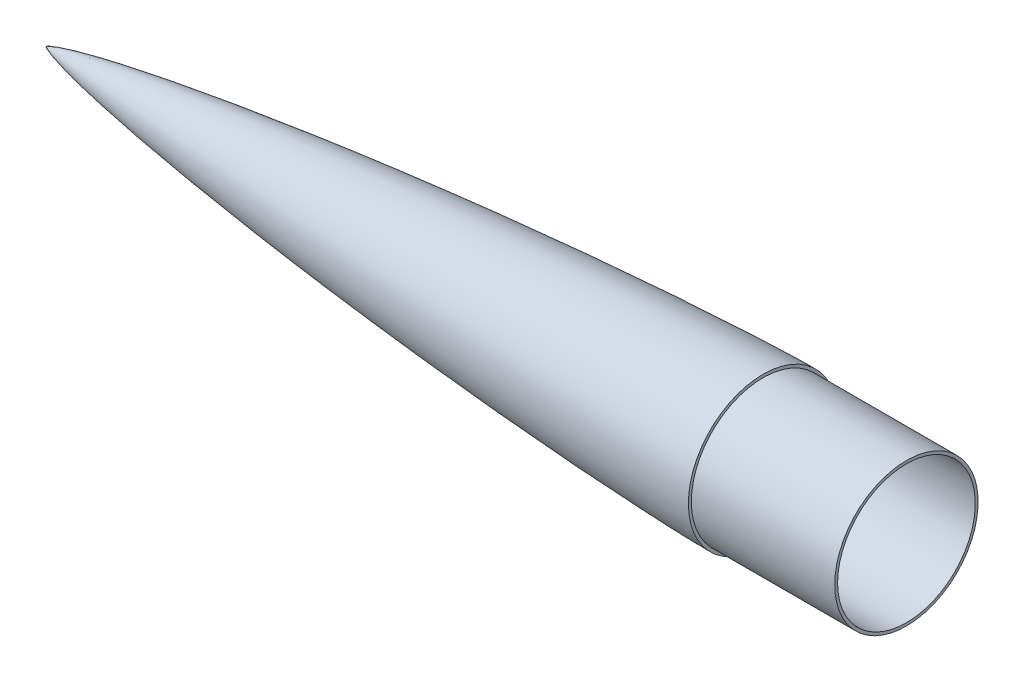
SolidWorks part; units mm, degrees
ref_plane "Front Plane" through (0, 0, 0) normal (0, 0, 1) x (1, 0, 0)
ref_plane "Top Plane" through (0, 0, 0) normal (0, 1, 0) x (1, 0, 0)
ref_plane "Right Plane" through (0, 0, 0) normal (1, 0, 0) x (0, 0, -1)
ref_axis "Axis1" through (-22.86, 0, 0) along (1, 0, 0)
sketch "Sketch1" plane through (0, 0, 0) normal (0, 0, 1) x (1, 0, 0)
  line L0 (381, 0) -> (0, 0)
  line L1 (251.46, 0) -> (-251.46, 0) construction
  line L2 (381, 0) -> (381, 36.576)
  line L4 (381, 38.1) -> (457.2, 38.1)
  line L5 (457.2, 38.1) -> (457.2, 36.576)
  line L6 (457.2, 36.576) -> (381, 36.576)
  line L7 (381, 38.1) -> (381, 39.6748)
  spline S0 degree 4 poles (0, 0) (0.003, 0.0074) (0.0105, 0.0213) (0.0311, 0.0458) (0.0656, 0.0788) (0.1085, 0.1142) (0.1696, 0.1593) (0.2429, 0.2084) (0.3536, 0.2764) (0.5216, 0.37) (0.7712, 0.4962) (1.1804, 0.6832) (1.8685, 0.9654) (3.0994, 1.4129) (5.367, 2.1346) (9.5884, 3.2967) (16.8729, 5.0187) (29.3641, 7.5637) (46.5722, 10.5749) (67.5031, 13.8025) (90.9083, 17.0332) (114.35, 19.9843) (137.8197, 22.7032) (161.3118, 25.2203) (184.8229, 27.5534) (208.3505, 29.7136) (231.8929, 31.7062) (255.4488, 33.5316) (279.0174, 35.1854) (302.5981, 36.6571) (323.2415, 37.7687) (340.9432, 38.5739) (355.1716, 39.1048) (364.7115, 39.3936) (372.5129, 39.5736) (377.3625, 39.648) (379.7875, 39.6717) (381, 39.6748) knots 0 0 0 0 0 0.000083 0.000166 0.000331 0.000497 0.000662 0.000957 0.001251 0.00185 0.002667 0.00387 0.005939 0.009599 0.016314 0.028666 0.051563 0.087599 0.14916 0.21072 0.272281 0.333842 0.395403 0.456964 0.518524 0.580085 0.641646 0.703207 0.764768 0.826328 0.887889 0.91867 0.94945 0.974725 0.987363 1 1 1 1 1 construction
  spline S1 degree 4 poles (0, 0) (0.003, 0.0074) (0.0105, 0.0213) (0.0311, 0.0458) (0.0656, 0.0788) (0.1085, 0.1142) (0.1696, 0.1593) (0.2429, 0.2084) (0.3536, 0.2764) (0.5216, 0.37) (0.7712, 0.4962) (1.1804, 0.6832) (1.8685, 0.9654) (3.0994, 1.4129) (5.367, 2.1346) (9.5884, 3.2967) (16.8729, 5.0187) (29.3641, 7.5637) (46.5722, 10.5749) (67.5031, 13.8025) (90.9083, 17.0332) (114.35, 19.9843) (137.8197, 22.7032) (161.3118, 25.2203) (184.8229, 27.5534) (208.3505, 29.7136) (231.8929, 31.7062) (255.4488, 33.5316) (279.0174, 35.1854) (302.5981, 36.6571) (323.2415, 37.7687) (340.9432, 38.5739) (355.1716, 39.1048) (364.7115, 39.3936) (372.5129, 39.5736) (377.3625, 39.648) (379.7875, 39.6717) (381, 39.6748) knots 0 0 0 0 0 0.000083 0.000166 0.000331 0.000497 0.000662 0.000957 0.001251 0.00185 0.002667 0.00387 0.005939 0.009599 0.016314 0.028666 0.051563 0.087599 0.14916 0.21072 0.272281 0.333842 0.395403 0.456964 0.518524 0.580085 0.641646 0.703207 0.764768 0.826328 0.887889 0.91867 0.94945 0.974725 0.987363 1 1 1 1 1
  point P2 (0, 0)
  point P7 (457.2, 36.576)
  point P8 (59.2451, 23.4245)
  point P10 (76.2, 36.576)
  point P13 (0, 0)
  point P14 (0, 39.6748)
  point P15 (-381, 0)
  point P16 (0, 0)
  point P17 (0, 36.576)
  point P18 (0, 38.1)
  point P19 (0, 39.6748)
  point P20 (-312.5778, -1.1743)
  point P21 (0, 0)
  point P26 (0, 0)
  point P27 (0, 0)
  dimension "D1" = 39.6748
  dimension "D2" = 38.1
  dimension "D3" = 36.576
  dimension "D4" = 76.2
  dimension "D5" = 381
revolve "Revolve1" add sketch "Sketch1" angle 360 about axis through (-22.86, 0, 0) along (1, 0, 0) region at (238.233, 15.4887, 0)
equation "\"D_o\" = 3.124in"
equation "\"D_i\"= 3in"
equation "\"D_c\"= 2.88in"
equation "\"L\"= 15"
equation "\"L_s\"= 3in"
equation "\"D1@Sketch1\"=\"D_o\"/2"
equation "\"D2@Sketch1\"=\"D_i\"/2"
equation "\"D3@Sketch1\"=\"D_c\"/2"
equation "\"D4@Sketch1\"=\"L_s\""
equation "\"D5@Sketch1\"=\"L\""
